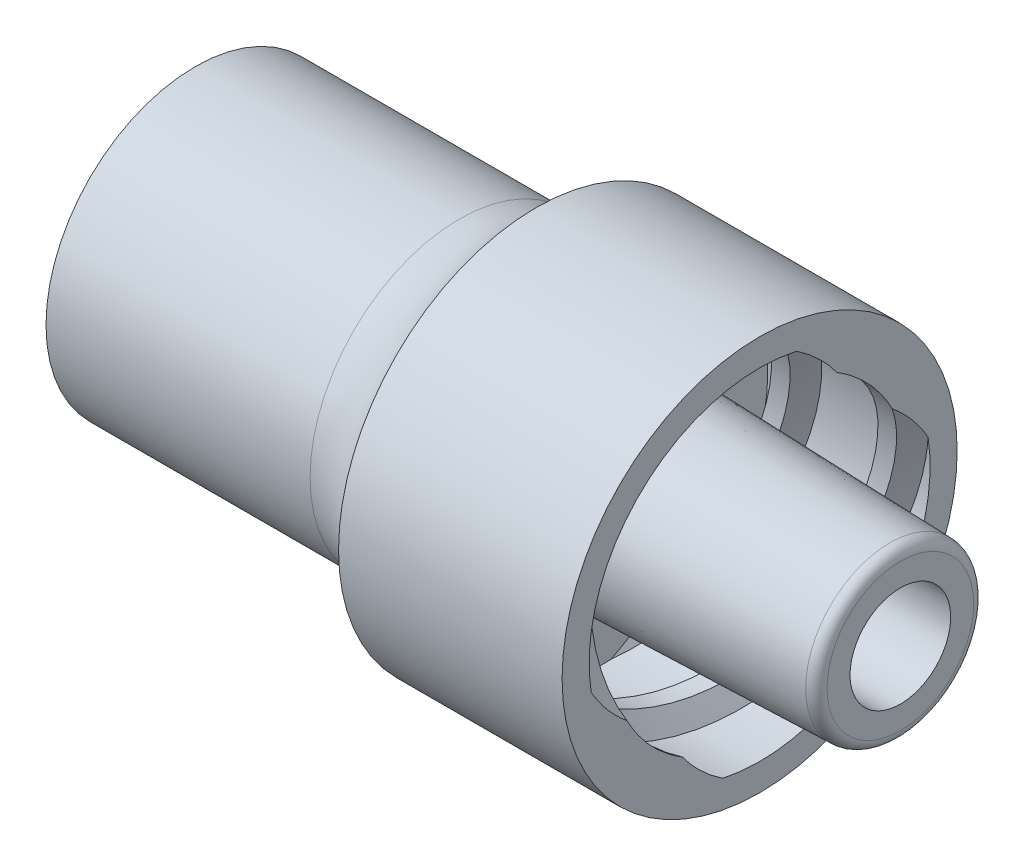
SolidWorks part; units mm, degrees
ref_plane "Front Plane" through (0, 0, 0) normal (0, 0, 1) x (1, 0, 0)
ref_plane "Top Plane" through (0, 0, 0) normal (0, 1, 0) x (1, 0, 0)
ref_plane "Right Plane" through (0, 0, 0) normal (1, 0, 0) x (0, 0, -1)
ref_axis "Axis1" through (-153.0602, 0, 0) along (1, 0, 0)
sketch "Sketch1" plane through (0, 0, 0) normal (0, 0, 1) x (1, 0, 0)
  line L0 (-8.5471, 0) -> (1.2572, 0) construction
  line L1 (26.968, 0) -> (-26.968, 0) construction
  line L2 (-8.5471, 1.1811) -> (-8.5471, 4.6355)
  line L3 (-8.5471, 4.6355) -> (-3.302, 4.6355)
  line L4 (-3.302, 4.6355) -> (-3.302, 4.0005)
  line L5 (-3.302, 4.0005) -> (-7.112, 4.0005)
  line L6 (-7.112, 4.0005) -> (-7.112, 2.1806)
  line L7 (-7.112, 2.1806) -> (0, 1.9672)
  line L8 (0, 1.9672) -> (0, 1.1811)
  line L10 (0, -18.6469) -> (0, 18.6469) construction
  line L11 (-2.54, 2.0434) -> (0, 2.0434) construction
  line L12 (-8.5471, 1.1811) -> (0, 1.1811)
  dimension "D1" = 9.271
  dimension "D2" = 2.54
  dimension "D3" = 0.0762
  dimension "D4" = 3.9345
  dimension "D5" = 7.112
  dimension "D6" = 8.001
  dimension "D7" = 3.302
  dimension "D8" = 5.2451
  dimension "D9" = 2.3622
revolve "Revolve: Nozzle" add sketch "Sketch1" angle 360 about L0
ref_plane "Plane: Luer Thread Start" through (-0.1524, 0, 0) normal (1, 0, 0) x (0, 0, -1)
sketch "Sketch2" plane through (-0.1524, 0, 0) normal (1, 0, 0) x (0, 0, -1)
  circle A0 centre (0, 0) radius 4.0005
  dimension "D1" = 8.001
curve "Helix/Spiral: Luer" pitch 4.9987 height 12.7 radius 4.0005 centre (-0.1524, 0, 0) axis (-1, 0, 0) start towards (0, 1, 0)
sketch "Sketch3" plane through (0, 0, 0) normal (0, 0, 1) x (1, 0, 0)
  line L0 (-15.6793, 0) -> (-0.1524, 0) construction
  line L1 (-0.1524, 0) -> (-0.1524, 4.0005) construction
  line L2 (26.968, 0) -> (-26.968, 0) construction
  line L3 (-0.3708, 3.5052) -> (0.066, 3.5052)
  line L4 (0.066, 3.5052) -> (0.3238, 4.0005)
  line L5 (-0.3708, 3.5052) -> (-0.6287, 4.0005)
  line L6 (-0.6287, 4.0005) -> (0.3238, 4.0005)
  line L9 (-0.1524, -5.0991) -> (-0.1524, 5.0991) construction
  line L10 (-3.302, 4.0005) -> (-7.112, 4.0005) construction
  dimension "D1" = 7.0104
  dimension "D2" = 0.9525
  dimension "D3" = 27.5
sweep "Sweep: Luer" add profiles "Sketch3" path "Helix/Spiral: Luer"
pattern_circular "CirPattern: Luer" count 2 over 360 about axis through (-8.5471, 0, 0) along (-1, 0, 0) of "Sweep: Luer"
sketch "Sketch4" plane through (0, 0, 0) normal (0, 0, 1) x (1, 0, 0)
  line L0 (-15.6221, 0) -> (2.9119, 0) construction
  line L1 (26.968, 0) -> (-26.968, 0) construction
  line L2 (-3.302, 4.6355) -> (2.54, 4.6355)
  line L3 (0, 0) -> (0, 1.7207)
  line L4 (-3.302, 4.6355) -> (-3.302, 2.0663)
  line L5 (-3.302, 2.0663) -> (-0.2464, 1.9746)
  line L6 (0, 1.9672) -> (-7.112, 2.1806) construction
  line L7 (-3.302, 4.6355) -> (-8.5471, 4.6355) construction
  line L8 (-3.302, -4.6355) -> (-3.302, 4.6355) construction
  line L9 (0, -18.6469) -> (0, 18.6469) construction
  line L10 (0, 0) -> (2.54, 0)
  line L11 (2.54, 4.6355) -> (2.54, 0)
  line L12 (-3.302, 4.6355) -> (-8.5471, 4.6355) construction
  line L13 (-13.6271, 4.6355) -> (-8.5471, 4.6355)
  line L14 (-13.6271, 4.6355) -> (-13.6271, 0)
  line L15 (-13.6271, 0) -> (-8.5471, 0)
  line L16 (-8.5471, 4.6355) -> (-8.5471, 0)
  line L17 (-8.5471, 4.6355) -> (-8.5471, -4.6355) construction
  arc A0 (0, 1.7207) -> (-0.2464, 1.9746) centre (-0.254, 1.7207) ccw
  dimension "D1" = 0.254
  dimension "D2" = 2.54
  dimension "D3" = 5.08
revolve "Cut-Revolve: Luer" cut sketch "Sketch4" angle 360 about L0
sketch "Sketch7" plane through (-8.5471, 0, 0) normal (-1, 0, 0) x (0, 0, 1)
  circle A0 centre (0, 0) radius 3.5
  circle A2 centre (0, 0) radius 1.1811
  circle A3 centre (0, 0) radius 1.1811 construction
  dimension "D1" = 7
  dimension "D2" = 0
extrude "Boss-Extrude1" add sketch "Sketch7" along normal blind 8
fillet "Fillet1" radius 2 1 edges at (-8.5471, 0, 3.5)
